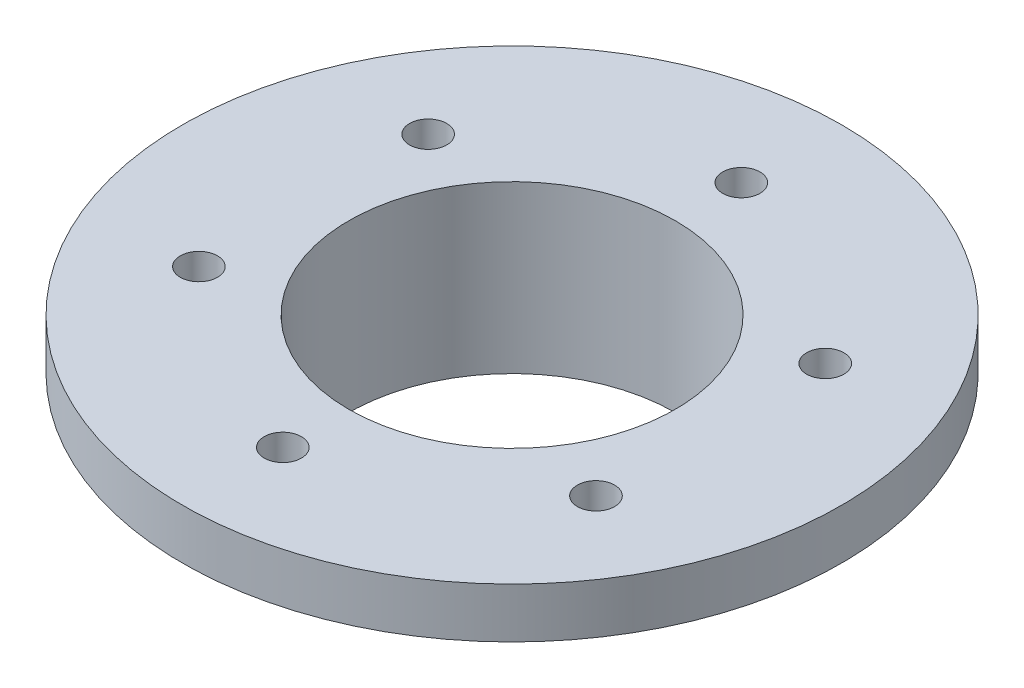
SolidWorks part; units mm, degrees
material "PBT General Purpose"
ref_plane "Front Plane" through (0, 0, 0) normal (0, 0, 1) x (1, 0, 0)
ref_plane "Top Plane" through (0, 0, 0) normal (0, 1, 0) x (1, 0, 0)
ref_plane "Right Plane" through (0, 0, 0) normal (1, 0, 0) x (0, 0, -1)
sketch "Sketch1" plane through (0, 0, 0) normal (1, 0, 0) x (0, 0, -1)
  line L0 (28.5, 60.1164) -> (57.5, 80.3684)
  line L5 (57.5, 80.3684) -> (57.5, 89.1164)
  line L6 (57.5, 89.1164) -> (28.5, 89.1164)
  line L7 (28.5, 89.1164) -> (28.5, 60.1164)
  line L8 (0, 0) -> (0, 88.6674) construction
  line L9 (31.6948, 62.3474) -> (58.0521, 80.754) construction
  dimension "D1" = 57.5
  dimension "D2" = 29
  dimension "D4" = 29
revolve "Revolve1" add sketch "Sketch1" angle 360 about L8
sketch "Sketch2" plane through (0, 89.1164, 0) normal (0, 1, 0) x (1, 0, 0)
  line L0 (0, -28.5) -> (0, -57.5) construction
  circle A0 centre (0, -40) radius 3.25
  circle A1 centre (0, 0) radius 28.5 construction
  circle A2 centre (0, 0) radius 57.5 construction
  circle A3 centre (-34.641, -20) radius 3.25
  circle A4 centre (-34.641, 20) radius 3.25
  circle A5 centre (0, 40) radius 3.25
  circle A6 centre (34.641, 20) radius 3.25
  circle A7 centre (34.641, -20) radius 3.25
  point P22 (0, 0)
  dimension "D2" = 6.5
  dimension "D3" = 40
  dimension "D1" = 6
extrude "Cut-Extrude1" cut sketch "Sketch2" against normal through all
sketch3d "3DSketch1"
  point P0 (-67.5, 59.1164, -67.5)
